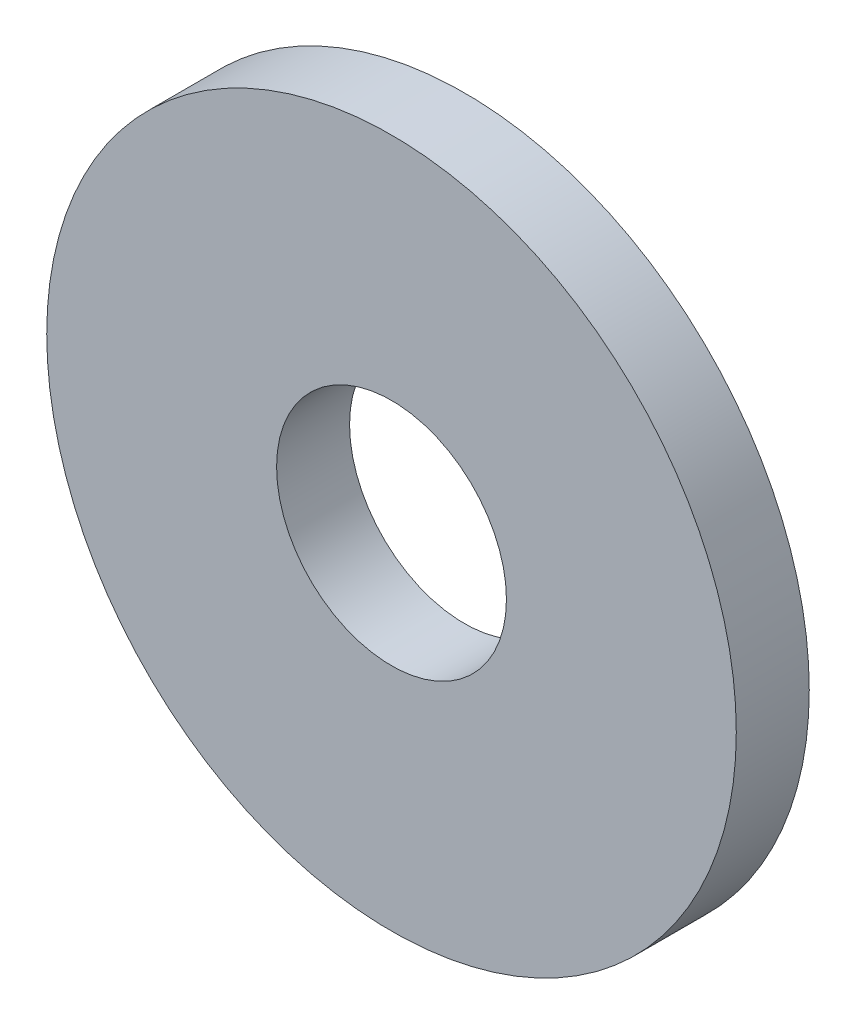
SolidWorks part; units mm, degrees
ref_plane "Front Plane" through (0, 0, 0) normal (0, 0, 1) x (1, 0, 0)
ref_plane "Top Plane" through (0, 0, 0) normal (0, 1, 0) x (1, 0, 0)
ref_plane "Right Plane" through (0, 0, 0) normal (1, 0, 0) x (0, 0, -1)
sketch "Sketch1" plane through (0, 0, 0) normal (0, 0, 1) x (1, 0, 0)
  circle A0 centre (0, 0) radius 2
  circle A1 centre (0, 0) radius 6
  dimension "D1" = 4
  dimension "D2" = 12
extrude "Boss-Extrude2" add sketch "Sketch1" along normal blind 1.27
